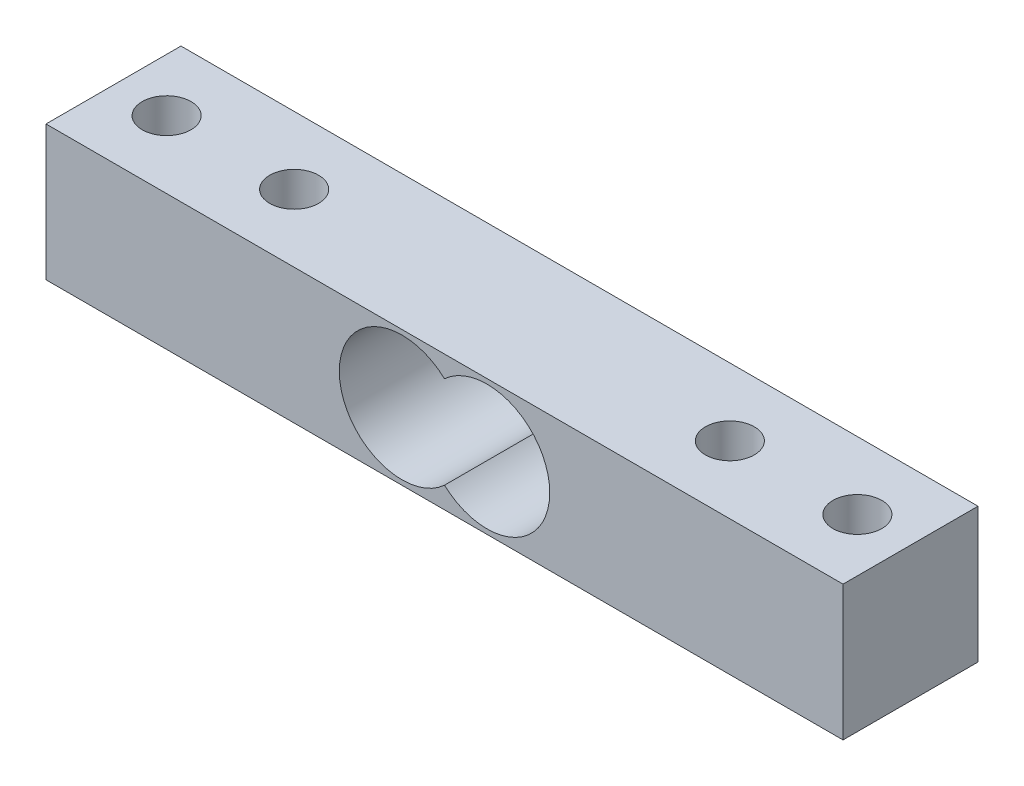
SolidWorks part; units mm, degrees
material "Aleación 1060"
ref_plane "Alzado" through (0, 0, 0) normal (0, 0, 1) x (1, 0, 0)
ref_plane "Planta" through (0, 0, 0) normal (0, 1, 0) x (1, 0, 0)
ref_plane "Vista lateral" through (0, 0, 0) normal (1, 0, 0) x (0, 0, -1)
sketch "Croquis2" plane through (0, 0, 0) normal (0, 0, 1) x (1, 0, 0)
  line L1 (-37.5, 6.35) -> (37.5, 6.35)
  line L2 (-37.5, 6.35) -> (-37.5, -6.35)
  line L3 (-37.5, -6.35) -> (37.5, -6.35)
  line L4 (37.5, 6.35) -> (37.5, -6.35)
  line L5 (-37.5, 6.35) -> (37.5, -6.35) construction
  line L6 (-37.5, -6.35) -> (37.5, 6.35) construction
  arc A1 (0, 4.337) -> (0, -4.337) centre (-4, 0) ccw
  arc A2 (0, -4.337) -> (0, 4.337) centre (4, 0) ccw
  point P0 (0, 0)
  dimension "D3" = 11.8
  dimension "D1" = 75
  dimension "D2" = 12.7
  dimension "D4" = 4
  dimension "D5" = 4
extrude "Saliente-Extruir1" add sketch "Croquis2" along normal mid plane 12.7
sketch "Croquis3" plane through (0, 6.35, 0) normal (0, 1, 0) x (1, 0, 0)
  line L0 (37.5, -6.35) -> (37.5, 6.35) construction
  line L1 (0, 0) -> (0, 10.7177) construction
  circle A0 centre (32.5, 0) radius 2.3
  circle A1 centre (20.5, 0) radius 2.3
  circle A2 centre (-32.5, 0) radius 2.3
  circle A3 centre (-20.5, 0) radius 2.3
  dimension "D1" = 4.6
  dimension "D2" = 5
  dimension "D3" = 12
extrude "Cortar-Extruir1" cut sketch "Croquis3" against normal through all
